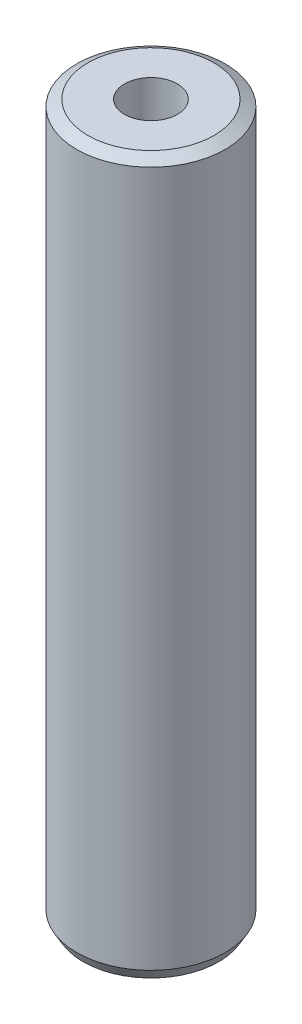
SolidWorks part; units mm, degrees
ref_plane "Front Plane" through (0, 0, 0) normal (0, 0, 1) x (1, 0, 0)
ref_plane "Top Plane" through (0, 0, 0) normal (0, 1, 0) x (1, 0, 0)
ref_plane "Right Plane" through (0, 0, 0) normal (1, 0, 0) x (0, 0, -1)
sketch "Sketch1" plane through (0, 0, 0) normal (0, 1, 0) x (1, 0, 0)
  circle A0 centre (0, 0) radius 12.5
  dimension "SHAFT_OD" = 25
extrude "Boss-Extrude1" add sketch "Sketch1" along normal blind 120.0636
sketch "Sketch2" plane through (0, 0, 0) normal (0, 1, 0) x (1, 0, 0)
  circle A0 centre (0, 0) radius 4.4514
  dimension "BORE_D" = 8.9029
extrude "Cut-Extrude1" cut sketch "Sketch2" along normal through all
chamfer "Chamfer1" distance 1.0918 angle 60 2 edges at (0, 120.0636, 12.5) (0, 0, 12.5) first distance on face at (0, 120.0636, 12.5) first distance on face at (0, 0, 4.4514)
